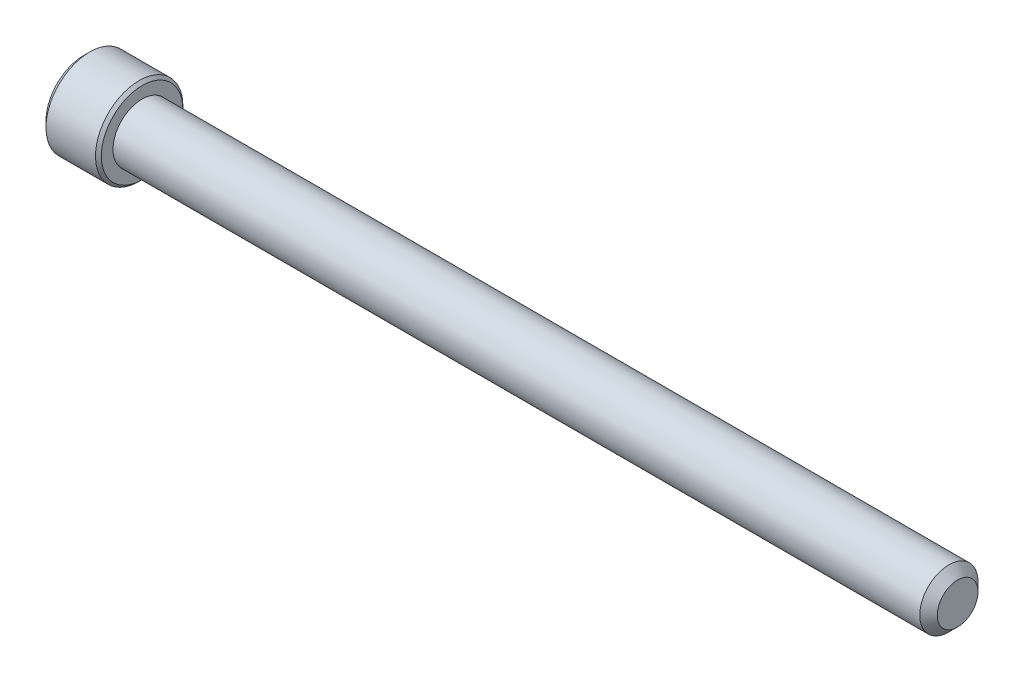
SolidWorks part; units mm, degrees
material "Alloy Steel"
ref_plane "Front Plane" through (0, 0, 0) normal (0, 0, 1) x (1, 0, 0)
ref_plane "Top Plane" through (0, 0, 0) normal (0, 1, 0) x (1, 0, 0)
ref_plane "Right Plane" through (0, 0, 0) normal (1, 0, 0) x (0, 0, -1)
sketch "Sketch1" plane through (0, 0, 0) normal (0, 0, 1) x (1, 0, 0)
  line L0 (44.45, 0) -> (-44.45, 0) construction
  line L1 (44.45, 3.175) -> (44.45, -3.175) construction
  line L2 (-44.45, 4.445) -> (-44.45, -4.445) construction
  line L3 (-44.7675, 4.7625) -> (-50.165, 4.7625) construction
  line L4 (-50.165, 4.7625) -> (-50.8, 4.1275) construction
  line L5 (-50.8, 4.1275) -> (-50.8, -4.1275) construction
  line L6 (-50.8, -4.1275) -> (-50.165, -4.7625) construction
  line L7 (-50.165, -4.7625) -> (-44.7675, -4.7625) construction
  line L8 (-44.7675, 4.7625) -> (-44.45, 4.445) construction
  line L9 (-44.45, -4.445) -> (-44.7675, -4.7625) construction
  point P5 (-44.45, 4.7625)
  point P6 (-44.45, -4.7625)
  point P7 (-47.752, 0)
  point P12 (39.37, -3.175)
  dimension "D1" = 45
  dimension "Dec." = 6.35
  dimension "Length" = 88.9
  dimension "Head Dia" = 9.525
  dimension "Head Height" = 6.35
  dimension "Hex Depth" = 3.048
  dimension "Chamfer" = 0.635
  dimension "D2" = 5.08
  dimension "D3" = 0.3175
  dimension "D4" = 45
ref_plane "Plane1" through (44.45, 0, 0) normal (1, 0, 0) x (0, 0, -1)
ref_plane "Plane2" through (-50.8, 0, 0) normal (1, 0, 0) x (0, 0, -1)
sketch "Sketch2" plane through (44.45, 0, 0) normal (1, 0, 0) x (0, 0, -1)
  circle A0 centre (0, 0) radius 3.175
extrude "Boss-Extrude1" add sketch "Sketch2" against normal up to vertex (88.9 mm away) up to point (-44.45, 0, 0)
sketch "Sketch3" plane through (44.45, 0, 0) normal (1, 0, 0) x (0, 0, -1)
  circle A0 centre (0, 0) radius 3.175 construction
  circle A1 centre (0, 0) radius 3.175
curve "Helix/Spiral1" pitch 1.27 height 90.17 turns 71 parameters "Pitch"=1.27
chamfer "Chamfer1" distance 0.9525 angle 45 1 edges at (44.45, 0, -3.175)
sketch "Sketch5" plane through (0, 0, 0) normal (0, 0, 1) x (1, 0, 0)
  line L0 (43.8944, 3.175) -> (45.0056, 3.175)
  line L1 (45.0056, 3.175) -> (44.5294, 2.3501)
  line L2 (44.5294, 2.3501) -> (44.3706, 2.3501)
  line L3 (44.3706, 2.3501) -> (43.8944, 3.175)
  line L4 (44.45, 2.3501) -> (44.45, 3.175) construction
  line L5 (44.1325, 2.7626) -> (44.7675, 2.7626) construction
  dimension "D1" = 60
  dimension "D2" = 0.635
  dimension "D3" = 0.1588
sweep "Cut-Sweep1" [suppressed] cut profiles "Sketch5" path "Helix/Spiral1"
sketch "Sketch4" plane through (-50.8, 0, 0) normal (1, 0, 0) x (0, 0, -1)
  line L0 (-4.7625, 0.7937) -> (4.7625, 0.7937) construction
  line L1 (0, 2.7496) -> (-2.3812, 1.3748)
  line L2 (-2.3812, 1.3748) -> (-2.3812, -1.3748)
  line L3 (-2.3812, -1.3748) -> (0, -2.7496)
  line L4 (0, -2.7496) -> (2.3813, -1.3748)
  line L5 (2.3813, -1.3748) -> (2.3813, 1.3748)
  line L6 (2.3813, 1.3748) -> (0, 2.7496)
  line L7 (0, 0) -> (0, 0.7937) construction
  circle A0 centre (0, 0) radius 2.3813 construction
  dimension "Hex Size" = 4.7625
  dimension "D1" = 9.525
  dimension "D2" = 0.7937
sketch "Sketch6" plane through (0, 0, 0) normal (0, 0, 1) x (1, 0, 0)
  line L0 (-50.165, 4.7625) -> (-50.8, 4.1275) construction
  line L2 (-44.45, 4.445) -> (-44.45, -4.445) construction
  line L3 (-50.8, 4.1275) -> (-50.8, -4.1275) construction
  line L4 (-50.165, 4.7625) -> (-50.8, 4.1275)
  line L5 (-44.7675, 4.7625) -> (-50.165, 4.7625) construction
  line L6 (-44.45, 4.445) -> (-44.45, 0)
  line L7 (-50.8, 4.1275) -> (-50.8, 0)
  line L8 (-44.45, 0) -> (-50.8, 0) construction
  line L9 (-44.45, 0) -> (-50.8, 0)
  line L10 (-44.7675, 4.7625) -> (-44.45, 4.445) construction
  line L11 (-44.7675, 4.7625) -> (-50.165, 4.7625)
  line L12 (-44.7675, 4.7625) -> (-44.45, 4.445)
revolve "Revolve1" add sketch "Sketch6" angle 360 about L8
extrude "Cut-Extrude1" cut sketch "Sketch4" along normal up to vertex (3.048 mm away) up to point (-47.752, 0, 0)
sketch "Sketch8" plane through (-50.8, 0, 0) normal (-1, 0, 0) x (0, 0, 1)
  circle A1 centre (0, 0) radius 2.7496
extrude "Cut-Extrude2" cut sketch "Sketch8" against normal blind 1.27 draft 45
equation "\"D3@Helix/Spiral1\" = \"Length@Sketch1\"+\"Pitch@Helix/Spiral1\""
equation "\"D3@Sketch5\" = \"Pitch@Helix/Spiral1\"*.125"
equation "\"D2@Sketch5\" = \"Pitch@Helix/Spiral1\"*.50"
equation "\"D1@Chamfer1\" = \"Pitch@Helix/Spiral1\"*.75"
equation "\"D2@Sketch1\" = \"Pitch@Helix/Spiral1\"*4"
equation "\"D1@Sketch4\" = \"Head Dia@Sketch1\""
equation "\"Chamfer@Sketch1\" = \"Head Height@Sketch1\"/10"
equation "\"D3@Sketch1\" = \"Chamfer@Sketch1\"/2"
equation "\"D1@Cut-Extrude2\" = \"Chamfer@Sketch1\"*2"
